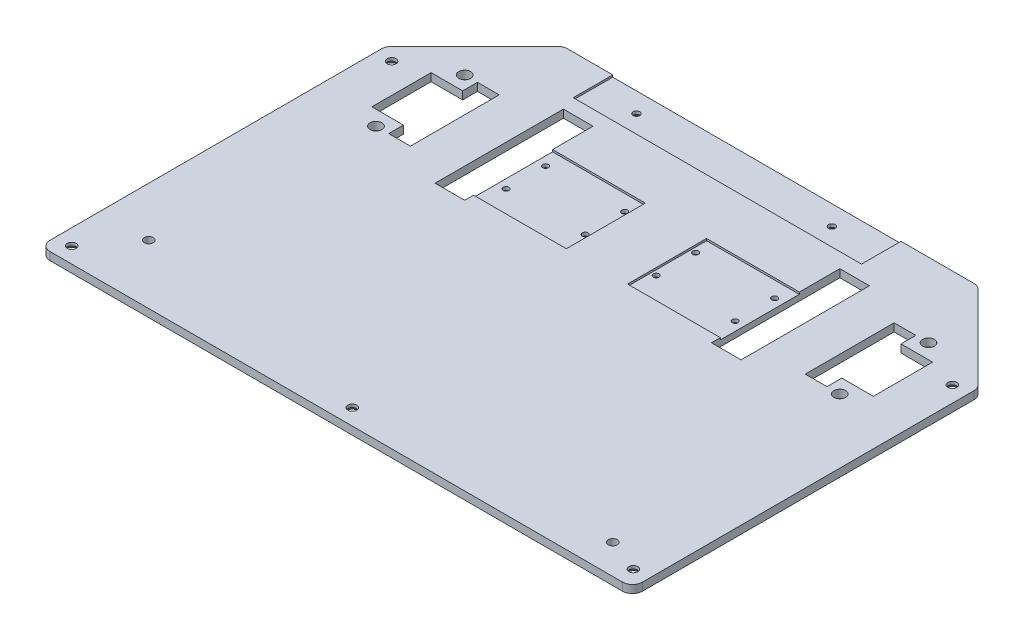
SolidWorks part; units mm, degrees
material "Acier non allié"
ref_plane "Front" through (0, 0, 0) normal (0, 0, 1) x (1, 0, 0)
ref_plane "Top" through (0, 0, 0) normal (0, 1, 0) x (1, 0, 0)
ref_plane "Right" through (0, 0, 0) normal (1, 0, 0) x (0, 0, -1)
sketch "Main scetch" plane through (0, 0, 0) normal (0, 1, 0) x (1, 0, 0)
  line L0 (-150, 0) -> (150, 0)
  line L1 (0, 0) -> (150, 0) construction
  line L2 (0, 0) -> (0, 220) construction
  line L3 (0, 220) -> (150, 220) construction
  line L4 (150, 0) -> (150, 220) construction
  line L5 (150, 0) -> (150, 175)
  line L6 (150, 175) -> (105, 220)
  line L10 (105, 220) -> (-105, 220)
  line L11 (-150, 0) -> (-150, 175)
  line L12 (-150, 175) -> (-105, 220)
  dimension "D1" = 150
  dimension "D2" = 220
  dimension "D3" = 45
  dimension "D4" = 45
extrude "Main extrusion" add sketch "Main scetch" along normal blind 4
fillet "Corner leave" radius 5 6 edges at (-150, 2, 0) (150, 2, -175) (105, 2, -220) (150, 2, 0) (-105, 2, -220) (-150, 2, -175)
sketch "Esquisse2" plane through (0, 4, 0) normal (0, 1, 0) x (1, 0, 0)
  line L0 (-145, 0) -> (145, 0) construction
  line L1 (150, 5) -> (150, 172.9289) construction
  line L2 (148.5355, 176.4645) -> (106.4645, 218.5355) construction
  line L3 (102.9289, 220) -> (-102.9289, 220) construction
  line L4 (-106.4645, 218.5355) -> (-148.5355, 176.4645) construction
  line L5 (-150, 172.9289) -> (-150, 5) construction
  line L6 (-145, 0) -> (145, 0) construction
  line L7 (150, 5) -> (150, 172.9289) construction
  line L8 (148.5355, 176.4645) -> (106.4645, 218.5355) construction
  line L9 (102.9289, 220) -> (-102.9289, 220) construction
  line L10 (-106.4645, 218.5355) -> (-148.5355, 176.4645) construction
  line L11 (-150, 172.9289) -> (-150, 5) construction
  line L12 (0, 0) -> (0, 238.9669) construction
  line L13 (0, 160) -> (165.6987, 160) construction
  line L14 (70, 230.4421) -> (70, 102.0601) construction
  line L15 (62.5, 192.5) -> (77.5, 192.5)
  line L16 (62.5, 192.5) -> (62.5, 127.5)
  line L17 (62.5, 127.5) -> (77.5, 127.5)
  line L18 (77.5, 192.5) -> (77.5, 127.5)
  line L19 (100, 137.5) -> (100, 182.5)
  line L20 (100, 182.5) -> (111, 182.5)
  line L22 (127, 175) -> (127, 145)
  line L23 (100, 137.5) -> (111, 137.5)
  line L35 (111, 182.5) -> (111, 175)
  line L36 (111, 175) -> (127, 175)
  line L37 (111, 137.5) -> (111, 145)
  line L38 (111, 145) -> (127, 145)
  line L39 (-111, 137.5) -> (-111, 145)
  line L40 (-100, 137.5) -> (-111, 137.5)
  line L41 (-100, 137.5) -> (-100, 182.5)
  line L42 (-100, 182.5) -> (-111, 182.5)
  line L43 (-111, 182.5) -> (-111, 175)
  line L44 (-111, 175) -> (-127, 175)
  line L45 (-127, 175) -> (-127, 145)
  line L46 (-111, 145) -> (-127, 145)
  line L47 (-62.5, 127.5) -> (-77.5, 127.5)
  line L48 (-77.5, 192.5) -> (-77.5, 127.5)
  line L49 (-62.5, 192.5) -> (-77.5, 192.5)
  line L50 (-62.5, 192.5) -> (-62.5, 127.5)
  circle A0 centre (117.47, 182.47) radius 3
  circle A1 centre (117.47, 137.53) radius 3
  circle A2 centre (-117.47, 137.53) radius 3
  circle A3 centre (-117.47, 182.47) radius 3
  point P28 (127, 160)
  point P29 (100, 160)
  dimension "D12" = 6
  dimension "D1" = 60
  dimension "D2" = 65
  dimension "D3" = 70
  dimension "D4" = 15
  dimension "D5" = 27
  dimension "D6" = 45
  dimension "D7" = 100
  dimension "D8" = 11
  dimension "D9" = 30
  dimension "D10" = 17.47
  dimension "D11" = 22.47
extrude "Enlèv. mat.-Extru.1" cut sketch "Esquisse2" against normal through all
sketch "Esquisse8" plane through (0, 4, 0) normal (0, 1, 0) x (1, 0, 0)
  line L0 (-150, 172.9289) -> (-150, 5) construction
  line L1 (-145, 0) -> (145, 0) construction
  line L3 (150, 5) -> (150, 172.9289) construction
  circle A0 centre (-125, 30) radius 1.5
  circle A1 centre (125, 15) radius 1.5
  circle A2 centre (-125, 12.5) radius 1
  circle A3 centre (-125, 47.5) radius 1
  dimension "D1" = 3
  dimension "D4" = 3
  dimension "D6" = 25
  dimension "D7" = 2
  dimension "D8" = 2
  dimension "D2" = 25
  dimension "D3" = 30
  dimension "D5" = 15
  dimension "D9" = 17.5
  dimension "D10" = 17.5
hole_wizard "Dégagement M41" positions "Esquisse16" profile "Esquisse17" hole size "M4" standard "ISO" end condition through all
sketch "Esquisse16" plane through (0, 4, 0) normal (0, 1, 0) x (1, 0, 0)
  point P0 (-125, 30)
  point P3 (125, 15)
sketch "Esquisse17" plane through (-125, 4, -30) normal (1, 0, 0) x (0, 0, 1)
  line L0 (0, 0) -> (0, 4)
  line L1 (0, 4) -> (2.25, 4)
  line L2 (2.25, 4) -> (2.25, 0)
  line L5 (2.25, 0) -> (0, 0)
  line L11 (0, -6.35) -> (0, 107.95) construction
  dimension "Diamètre du perçage jusqu'au prochain" = 4.5
  dimension "Profondeur du perçage jusqu'au prochain" = 4
sketch "Esquisse18" plane through (0, 4, 0) normal (0, 1, 0) x (1, 0, 0)
  line L0 (-150, 172.9289) -> (-150, 5) construction
  line L1 (-145, 0) -> (145, 0) construction
  line L3 (150, 5) -> (150, 172.9289) construction
  circle A0 centre (-142, 8) radius 1
  circle A1 centre (-142, 170) radius 1
  circle A4 centre (142, 170) radius 1
  circle A5 centre (142, 8) radius 1
  circle A6 centre (0, 8) radius 1.5
  dimension "D1" = 2
  dimension "D2" = 2
  dimension "D3" = 3
  dimension "D4" = 8
  dimension "D5" = 2
  dimension "D6" = 2
  dimension "D7" = 8
  dimension "D8" = 8
  dimension "D9" = 170
  dimension "D10" = 8
  dimension "D15" = 8
  dimension "D16" = 170
  dimension "D17" = 8
  dimension "D18" = 8
sketch "Esquisse23" plane through (0, 4, 0) normal (0, 1, 0) x (1, 0, 0)
  line L0 (-62.5, 127.5) -> (-62.5, 192.5) construction
  line L1 (-62.5, 172) -> (-15.5, 172)
  line L2 (-62.5, 172) -> (-62.5, 132)
  line L3 (-62.5, 132) -> (-15.5, 132)
  line L4 (-15.5, 172) -> (-15.5, 132)
  line L6 (-62.5, 160) -> (-12.8793, 160) construction
  point P8 (0, 0)
  point P9 (-62.5, 160)
  dimension "D1" = 40
  dimension "D2" = 47
  dimension "D3" = 12
extrude "Enlèv. mat.-Extru.2" cut sketch "Esquisse23" against normal blind 1
sketch "Esquisse24" plane through (0, 3, 0) normal (0, 1, 0) x (1, 0, 0)
  line L0 (-58, 212.7511) -> (-58, 75.2489) construction
  line L1 (-62.5, 172) -> (-62.5, 132) construction
  line L2 (-15.5, 172) -> (-62.5, 172) construction
  line L3 (-18, 126.9657) -> (-18, 195.1017) construction
  line L4 (-58, 164) -> (-9.2469, 164) construction
  line L5 (-58, 144) -> (-13.1999, 144) construction
  circle A0 centre (-58, 164) radius 1
  circle A1 centre (-58, 144) radius 1
  circle A2 centre (-18, 164) radius 1
  circle A3 centre (-18, 144) radius 1
  dimension "D1" = 2
  dimension "D2" = 2
  dimension "D7" = 2
  dimension "D8" = 2
  dimension "D3" = 20
  dimension "D4" = 4.5
  dimension "D5" = 8
  dimension "D6" = 40
extrude "Enlèv. mat.-Extru.3" cut sketch "Esquisse24" against normal through all
hole_wizard "Fraisage pour vis à tête fraisée M2.51" positions "Esquisse27" profile "Esquisse28" countersink size "M2.5" standard "ISO" end condition through all
sketch "Esquisse27" plane through (0, 0, 0) normal (0, -1, 0) x (-1, 0, 0)
  point P0 (18, 164)
  point P3 (58, 164)
  point P6 (58, 144)
  point P9 (18, 144)
sketch "Esquisse28" plane through (-18, 0, -164) normal (1, 0, 0) x (0, 0, -1)
  line L0 (0, 0) -> (0, 4)
  line L1 (0, 4) -> (1.45, 4)
  line L2 (1.45, 4) -> (1.45, 1.3)
  line L3 (1.45, 1.3) -> (2.75, 0)
  line L5 (2.75, 0) -> (0, 0)
  line L6 (-1.45, 1.3) -> (-2.75, 0) construction
  line L11 (0, -6.35) -> (0, 107.95) construction
  dimension "Diamètre du perçage jusqu'au prochain" = 2.9
  dimension "Profondeur du perçage jusqu'au prochain" = 4
  dimension "Diamètre du fraisage entrant" = 5.5
  dimension "Angle du fraisage entrant" = 90
mirror "Symétrie1" about plane through (0, 0, 0) normal (1, 0, 0) of "Enlèv. mat.-Extru.3", "Fraisage pour vis à tête fraisée M2.51", "Enlèv. mat.-Extru.2"
hole_wizard "Fraisage pour vis à tête fraisée M41" positions "Esquisse30" profile "Esquisse31" countersink size "M4" standard "ISO" end condition through all
sketch "Esquisse30" plane through (0, 0, 0) normal (0, -1, 0) x (-1, 0, 0)
  point P0 (-142.0349, 8.4348)
  point P2 (0, 8.1016)
  point P4 (0, 8.1016)
  point P6 (142, 8)
  point P9 (142, 170)
  point P12 (-142, 170)
sketch "Esquisse31" plane through (142.0349, 0, -8.4348) normal (1, 0, 0) x (0, 0, -1)
  line L0 (0, 0) -> (0, 4)
  line L1 (0, 4) -> (2.25, 4)
  line L2 (2.25, 4) -> (2.25, 2.45)
  line L3 (2.25, 2.45) -> (4.7, 0)
  line L5 (4.7, 0) -> (0, 0)
  line L6 (-2.25, 2.45) -> (-4.7, 0) construction
  line L11 (0, -6.35) -> (0, 107.95) construction
  dimension "Diamètre du perçage jusqu'au prochain" = 4.5
  dimension "Profondeur du perçage jusqu'au prochain" = 4
  dimension "Diamètre du fraisage entrant" = 9.4
  dimension "Angle du fraisage entrant" = 90
sketch "Esquisse32" plane through (0, 4, 0) normal (0, 1, 0) x (1, 0, 0)
  line L0 (102.9289, 220) -> (-102.9289, 220) construction
  line L1 (-80, 220) -> (66, 220)
  line L2 (-80, 220) -> (-80, 200)
  line L3 (-80, 200) -> (66, 200)
  line L4 (66, 220) -> (66, 200)
  line L5 (150, 5) -> (150, 172.9289) construction
  dimension "D1" = 84
  dimension "D2" = 146
  dimension "D3" = 20
extrude "Enlèv. mat.-Extru.4" cut sketch "Esquisse32" against normal blind 1
sketch "Esquisse33" plane through (0, 0, 0) normal (0, -1, 0) x (1, 0, 0)
  line L4 (-80, -200) -> (-80, -220)
  line L5 (66, -200) -> (-80, -200)
  line L6 (66, -220) -> (66, -200)
  line L7 (-80, -220) -> (66, -220)
  line L8 (-80, -200) -> (-80, -220) construction
  line L9 (66, -200) -> (-80, -200) construction
  line L10 (66, -220) -> (66, -200) construction
  line L11 (-80, -220) -> (66, -220) construction
  circle A0 centre (-58, -210) radius 1
  circle A1 centre (41, -210) radius 1
  dimension "D4" = 2
  dimension "D7" = 2
  dimension "D2" = 22
  dimension "D3" = 10
  dimension "D5" = 25
  dimension "D6" = 10
  dimension "D1" = 0
extrude "Enlèv. mat.-Extru.5" cut sketch "Esquisse33" against normal through all
hole_wizard "Fraisage pour vis à tête fraisée M31" positions "Esquisse34" profile "Esquisse35" countersink size "M3" standard "ISO" end condition through all
sketch "Esquisse34" plane through (0, 0, 0) normal (0, -1, 0) x (-1, 0, 0)
  point P0 (58, 210)
  point P3 (-41, 210)
sketch "Esquisse35" plane through (-58, 0, -210) normal (1, 0, 0) x (0, 0, -1)
  line L0 (0, 0) -> (0, 4)
  line L1 (0, 4) -> (1.7, 4)
  line L2 (1.7, 4) -> (1.7, 1.45)
  line L3 (1.7, 1.45) -> (3.15, 0)
  line L5 (3.15, 0) -> (0, 0)
  line L6 (-1.7, 1.45) -> (-3.15, 0) construction
  line L11 (0, -6.35) -> (0, 107.95) construction
  dimension "Diamètre du perçage jusqu'au prochain" = 3.4
  dimension "Profondeur du perçage jusqu'au prochain" = 4
  dimension "Diamètre du fraisage entrant" = 6.3
  dimension "Angle du fraisage entrant" = 90
equation "\"WIDTH\"= 300mm'Total width of the robot"
equation "\"LENGTH\"= 220mm'Total length of the robot"
equation "\"D1@Main scetch\" = \"WIDTH\" / 2"
equation "\"D2@Main scetch\" = \"LENGTH\""
equation "\"CUT_DEPTH\"= 45mm'Depth of the cut on the edges of the plate"
equation "\"D3@Main scetch\" = \"CUT_DEPTH\""
equation "\"D4@Main scetch\" = \"CUT_DEPTH\""
equation "\"Plate_th\"= 3mm'Thickness of the plate"
equation "\"D1\"= \"Plate_th\""
